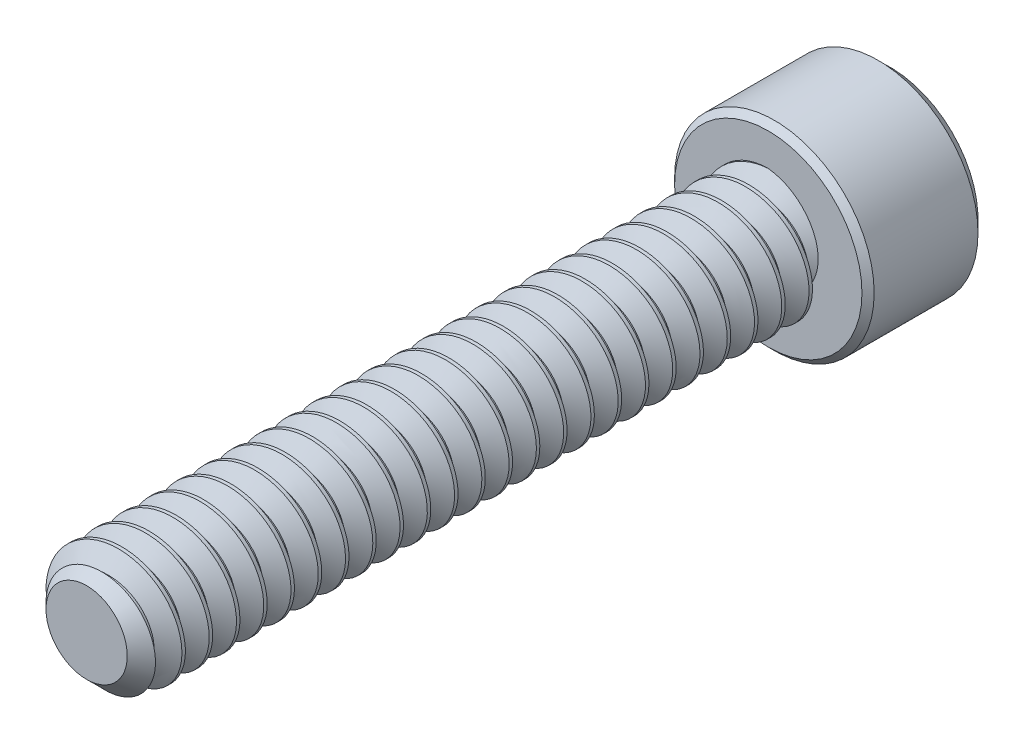
SolidWorks part; units mm, degrees
ref_plane "Front Plane" through (0, 0, 0) normal (0, 0, 1) x (1, 0, 0)
ref_plane "Top Plane" through (0, 0, 0) normal (0, 1, 0) x (1, 0, 0)
ref_plane "Right Plane" through (0, 0, 0) normal (1, 0, 0) x (0, 0, -1)
sketch "Sketch1" plane through (0, 0, 0) normal (0, 0, 1) x (1, 0, 0)
  line L0 (0, 1.4224) -> (0, -1.4224) construction
  circle A0 centre (0, 0) radius 1.4224
  dimension "OD" = 2.8448
extrude "Extrude1" add sketch "Sketch1" against normal blind 15.875
sketch "Sketch2" plane through (0, 0, 0) normal (0, 0, 1) x (1, 0, 0)
  circle A0 centre (0, 0) radius 1.4224 construction
  circle A1 centre (0, 0) radius 1.4224
curve "Helix/Spiral1" pitch 0.635 height 16.51 turns 26 parameters "pitch"=0.635
chamfer "Chamfer3" distance 0.4763 angle 45 1 edges at (1.4224, 0, 0)
sketch "Sketch3" plane through (0, 0, 0) normal (1, 0, 0) x (0, 0, -1)
  line L0 (-0.5556, 1.4224) -> (-0.3175, 1.01)
  line L1 (-0.3175, 1.01) -> (-0.2381, 1.01)
  line L2 (-0.2381, 1.01) -> (0, 1.4224)
  line L3 (-0.5556, 1.4224) -> (0, 1.4224)
  line L4 (-0.2778, 1.4224) -> (-0.2778, 1.01) construction
  line L5 (-0.4366, 1.2162) -> (-0.1191, 1.2162) construction
  line L6 (0, 1.4224) -> (0, -1.4224) construction
  dimension "D1" = 0.0794
  dimension "D2" = 0.3175
  dimension "D3" = 60
sweep "Cut-Sweep1" cut profiles "Sketch3" path "Helix/Spiral1"
sketch "Sketch6" plane through (0, 0, -15.875) normal (0, 0, -1) x (-1, 0, 0)
  circle A0 centre (0, 0) radius 2.3241
  dimension "head dia" = 4.6482
extrude "Extrude2" add sketch "Sketch6" along normal blind 2.8448
sketch "Sketch7" plane through (0, 0, -18.7198) normal (0, 0, -1) x (-1, 0, 0)
  line L1 (0, 1.3748) -> (-1.1906, 0.6874)
  line L2 (-1.1906, 0.6874) -> (-1.1906, -0.6874)
  line L3 (-1.1906, -0.6874) -> (0, -1.3748)
  line L4 (0, -1.3748) -> (1.1906, -0.6874)
  line L5 (1.1906, -0.6874) -> (1.1906, 0.6874)
  line L6 (1.1906, 0.6874) -> (0, 1.3748)
  circle A0 centre (0, 0) radius 1.1906 construction
  dimension "hex dia" = 2.3813
extrude "Cut-Extrude1" cut sketch "Sketch7" against normal blind 1.7859
sketch "Sketch8" plane through (0, 0, -18.7198) normal (0, 0, -1) x (-1, 0, 0)
  circle A0 centre (0, 0) radius 1.3748
extrude "Cut-Extrude2" cut sketch "Sketch8" against normal blind 0.2845 draft 45
chamfer "Chamfer1" distance 0.2845 angle 45 1 edges at (-2.3241, 0, -18.7198)
chamfer "Chamfer2" distance 0.1422 angle 45 1 edges at (-2.3241, 0, -15.875)
sketch "Sketch9" plane through (0, 0, 0) normal (1, 0, 0) x (0, 0, -1)
  line L0 (0, 1.4224) -> (0, -1.4224) construction
  line L1 (3.4925, 1.4224) -> (3.4925, -1.4224) construction
  line L2 (15.875, 2.3241) -> (15.875, -2.3241) construction
  line L3 (18.7198, 2.3241) -> (18.7198, -2.3241) construction
  line L4 (18.7198, 0) -> (0, 0) construction
  dimension "D1" = 3.4925
  dimension "D2" = 2.8448
  dimension "D3" = 4.6482
  dimension "D4" = 15.875
equation "\"D3@Helix/Spiral1\" = \"screw length@Extrude1\"+\"pitch@Helix/Spiral1\""
equation "\"D1@Sketch3\" = \"pitch@Helix/Spiral1\"*.125"
equation "\"D2@Sketch3\" = \"pitch@Helix/Spiral1\"*.5"
equation "\"D1@Cut-Extrude1\" = \"hex dia@Sketch7\"*.75"
equation "\"D1@Chamfer1\" = \"head depth@Extrude2\"/10"
equation "\"D1@Sketch9\" = \"pitch@Helix/Spiral1\"*5.5"
equation "\"D1@Chamfer2\" = \"D1@Chamfer1\"/2"
equation "\"D1@Cut-Extrude2\" = \"D1@Chamfer2\"*2"
equation "\"D1@Chamfer3\" = \"pitch@Helix/Spiral1\"*.750"
equation "\"D2@Sketch9\" = \"head depth@Extrude2\""
equation "\"D3@Sketch9\" = \"head dia@Sketch6\""
equation "\"D4@Sketch9\" = \"screw length@Extrude1\""
